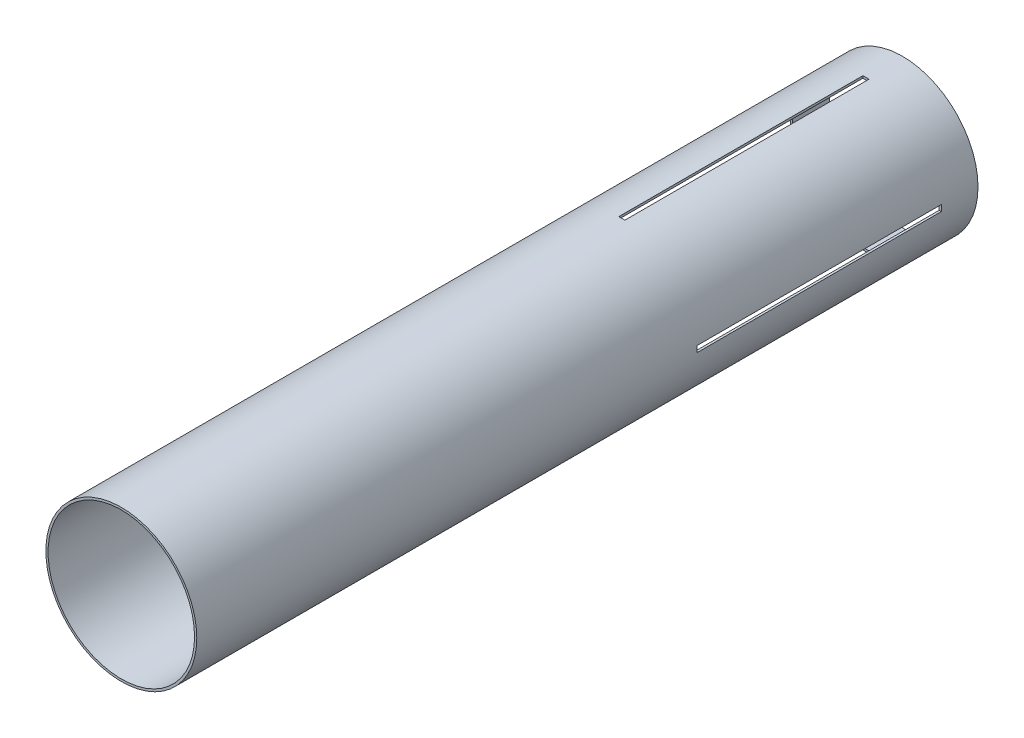
SolidWorks part; units mm, degrees
ref_plane "Front Plane" through (0, 0, 0) normal (0, 0, 1) x (1, 0, 0)
ref_plane "Top Plane" through (0, 0, 0) normal (0, 1, 0) x (1, 0, 0)
ref_plane "Right Plane" through (0, 0, 0) normal (1, 0, 0) x (0, 0, -1)
sketch "Sketch1" plane through (0, 0, 0) normal (0, 0, 1) x (1, 0, 0)
  circle A0 centre (0, 0) radius 39.2557
  circle A1 centre (0, 0) radius 38.1
  dimension "D2" = 78.5114
extrude "Boss-Extrude1" add sketch "Sketch1" along normal mid plane 406.4
sketch "Sketch3" plane through (0, 0, 0) normal (0, 1, 0) x (1, 0, 0)
  line L0 (39.2557, 203.2) -> (-39.2557, 203.2) construction
  line L1 (1.5875, 57.15) -> (-1.5875, 57.15)
  line L2 (1.5875, 57.15) -> (1.5875, 184.15)
  line L3 (1.5875, 184.15) -> (-1.5875, 184.15)
  line L4 (-1.5875, 57.15) -> (-1.5875, 184.15)
  line L5 (1.5875, 57.15) -> (-1.5875, 184.15) construction
  line L6 (1.5875, 184.15) -> (-1.5875, 57.15) construction
  line L7 (39.2557, 203.2) -> (-39.2557, 203.2) construction
  point P0 (0, 120.65)
  dimension "D1" = 3.175
  dimension "D2" = 127
  dimension "D3" = 19.05
extrude "Cut-Extrude1" cut sketch "Sketch3" along normal through all
pattern_circular "CirPattern1" count 4 over 360 about axis through (0, 0, 203.2) along (0, 0, -1) of "Cut-Extrude1" reverse direction yes
equation "\"AIRFRAME_OD\"= 3.091in"
equation "\"AIRFRAME_ID\"= 3.00in"
equation "\"FLAT_T\" = 0.125in"
equation "\"NOSE_EXP_L\"= 3.5in"
equation "\"NOSE_SHOULDER_L\" = 5in"
equation "\"MAIN_L\" = 30in"
equation "\"RECO_COUP_L\" = 6in"
equation "\"RECO_SWITCH_L\" = 1.5in"
equation "\"DROGUE_L\" = 14in"
equation "\"ATS_FORE_COUP_L\" = 4in"
equation "\"ATS_AFT_COUP_L\" = 4in"
equation "\"LOWER_L\" = 16in"
equation "\"FIN_N\" = 4"
equation "\"CR_AFT_X\" = 0.5in"
equation "\"CR_FORE_X\" = 6in"
equation "\"D1@Sketch1\"=\"AIRFRAME_ID\""
equation "\"D2@Sketch1\"=\"AIRFRAME_OD\""
equation "\"D1@Boss-Extrude1\"=\"LOWER_L\""
equation "\"FIN_ROOT\" = 5in"
equation "\"FIN_X\" = 0.75in"
equation "\"MOTOR_OD\" = 2.25in"
equation "\"MOTOR_ID\" = 2.126in"
equation "\"D1@Sketch3\"=\"FLAT_T\""
equation "\"D2@Sketch3\"=\"FIN_ROOT\""
equation "\"D3@Sketch3\"=\"FIN_X\""
equation "\"D1@CirPattern1\"=\"FIN_N\""
